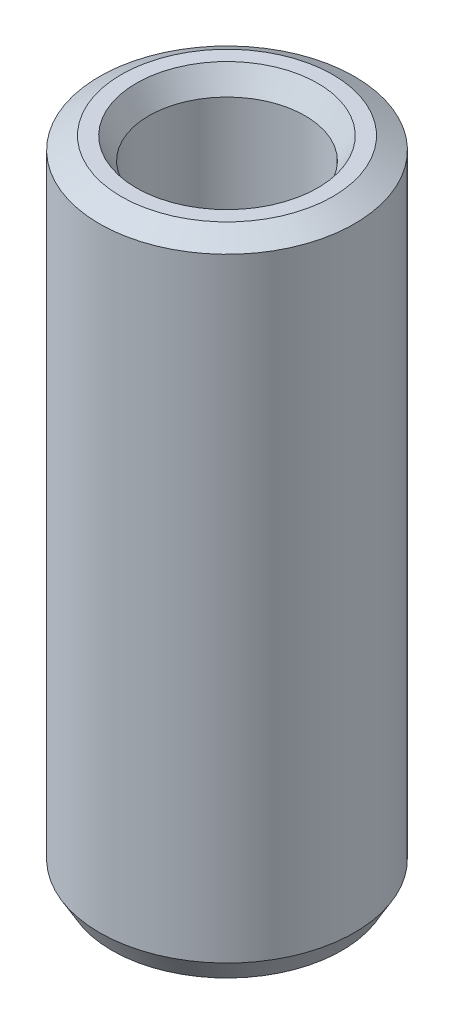
SolidWorks part; units mm, degrees
ref_plane "Front Plane" through (0, 0, 0) normal (0, 0, 1) x (1, 0, 0)
ref_plane "Top Plane" through (0, 0, 0) normal (0, 1, 0) x (1, 0, 0)
ref_plane "Right Plane" through (0, 0, 0) normal (1, 0, 0) x (0, 0, -1)
sketch "Sketch1" plane through (0, 0, 0) normal (0, 1, 0) x (1, 0, 0)
  circle A0 centre (0, 0) radius 27.5
  dimension "SLEEVE_OD" = 55
extrude "Boss-Extrude1" add sketch "Sketch1" along normal blind 139.7356
sketch "Sketch2" plane through (0, 0, 0) normal (0, 1, 0) x (1, 0, 0)
  circle A0 centre (0, 0) radius 16.8381
  dimension "BORE_D" = 33.6762
extrude "Cut-Extrude1" cut sketch "Sketch2" along normal through all
chamfer "Chamfer1" distance 2.7171 angle 60 4 edges at (0, 139.7356, 16.8381) (0, 0, 16.8381) (0, 0, 27.5) (0, 139.7356, 27.5) first distance on face at (0, 139.7356, 16.8381) first distance on face at (0, 0, 16.8381) first distance on face at (0, 139.7356, 27.5)
